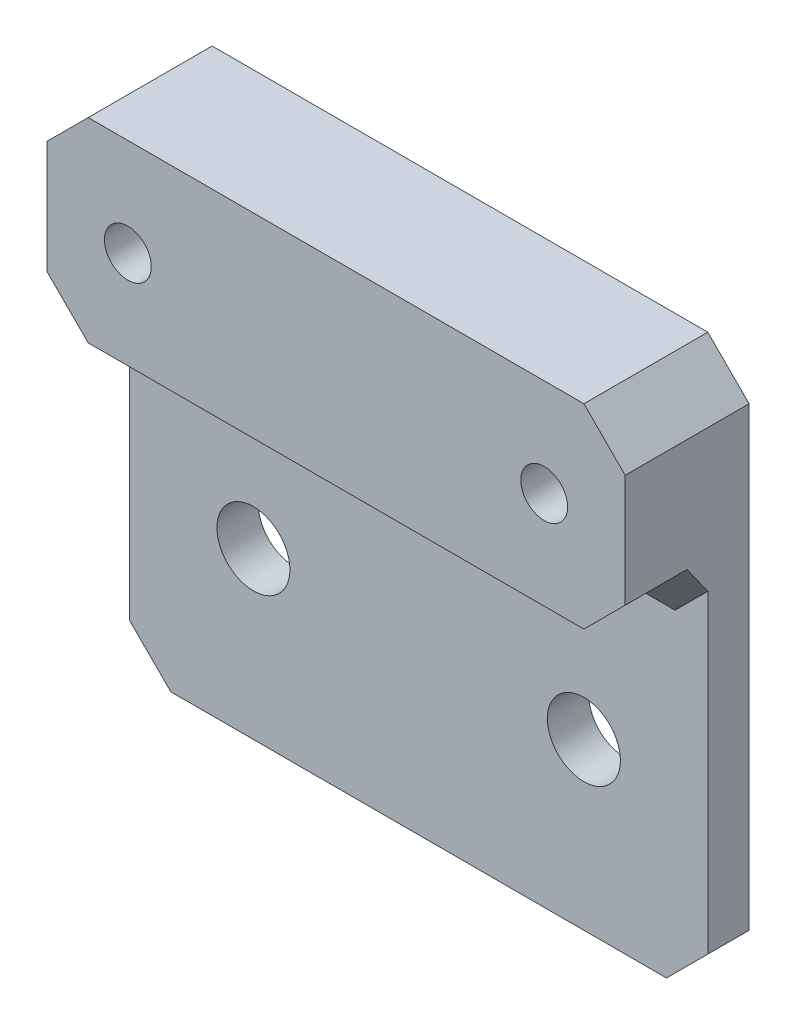
SolidWorks part; units mm, degrees
ref_plane "Front" through (0, 0, 0) normal (0, 0, 1) x (1, 0, 0)
ref_plane "Top" through (0, 0, 0) normal (0, 1, 0) x (1, 0, 0)
ref_plane "Right" through (0, 0, 0) normal (1, 0, 0) x (0, 0, -1)
sketch "Sketch1" plane through (0, 0, 0) normal (0, 0, 1) x (1, 0, 0)
  line L0 (-22.225, 0) -> (-12.7, 0) construction
  line L1 (-22.225, 12.7) -> (22.225, 12.7) construction
  line L2 (-22.225, 12.7) -> (-22.225, -12.7)
  line L3 (-22.225, -12.7) -> (22.225, -12.7)
  line L4 (22.225, 12.7) -> (22.225, -12.7)
  line L5 (-22.225, 12.7) -> (22.225, -12.7) construction
  line L6 (-22.225, -12.7) -> (22.225, 12.7) construction
  line L7 (-12.7, 0) -> (12.7, 0) construction
  line L8 (12.7, 0) -> (22.225, 0) construction
  line L9 (-22.225, 13.7) -> (-22.225, 28.7)
  line L10 (-22.225, 28.7) -> (22.225, 28.7)
  line L11 (22.225, 28.7) -> (22.225, 13.7)
  line L12 (-22.225, 13.7) -> (22.225, 13.7) construction
  line L13 (22.225, 13.7) -> (22.225, 12.7)
  line L14 (-22.225, 13.7) -> (-22.225, 12.7)
  point P0 (0, 0)
  dimension "D1" = 25.4
  dimension "D2" = 44.45
  dimension "D3" = 25.4
  dimension "D4" = 15
  dimension "D5" = 1
extrude "Boss-Extrude1" add sketch "Sketch1" along normal blind 3.175
sketch "Sketch2" plane through (0, 0, 3.175) normal (0, 0, 1) x (1, 0, 0)
  line L1 (-22.225, 28.7) -> (22.225, 28.7)
  line L2 (-22.225, 28.7) -> (-22.225, 13.7)
  line L3 (-22.225, 13.7) -> (22.225, 13.7)
  line L4 (22.225, 28.7) -> (22.225, 13.7)
  point P5 (0, 0)
  point P7 (0, 0)
  point P8 (20.5488, 16.1821)
extrude "Boss-Extrude2" add sketch "Sketch2" along normal blind 6.35
sketch "Sketch3" plane through (0, 0, 9.525) normal (0, 0, 1) x (1, 0, 0)
  line L0 (-22.225, 21.2) -> (-16, 21.2) construction
  line L1 (-22.225, 28.7) -> (-22.225, 13.7) construction
  line L2 (-16, 21.2) -> (16, 21.2) construction
  line L3 (16, 21.2) -> (22.225, 21.2) construction
  line L4 (22.225, 13.7) -> (22.225, 28.7) construction
  dimension "D1" = 32
hole_wizard "CBORE for M3 Hex Head Machine Screw1" positions "Sketch5" profile "Sketch6" counterbore size "M3" standard "ANSI Metric" end condition through all
sketch "Sketch5" plane through (0, 0, 0) normal (0, 0, -1) x (-1, 0, 0)
  point P0 (-16, 21.2)
  point P2 (16, 21.2)
  point P6 (0, 0)
sketch "Sketch6" plane through (16, 21.2, 0) normal (1, 0, 0) x (0, 1, 0)
  line L0 (0, 0) -> (0, 9.525)
  line L1 (0, 9.525) -> (1.8, 9.525)
  line L3 (1.8, 9.525) -> (1.8, 2.3)
  line L4 (1.8, 2.3) -> (4.2, 2.3)
  line L5 (4.2, 2.3) -> (4.2, 0)
  line L7 (4.2, 0) -> (0, 0)
  line L11 (0, -6.35) -> (0, 107.95) construction
  dimension "Thru Hole Dia." = 3.6
  dimension "Thru Hole Depth" = 9.525
  dimension "C'Bore Dia." = 8.4
  dimension "C'Bore Depth" = 2.3
chamfer "Chamfer2" distance 3.175 angle 45 6 edges at (22.225, 13.7, 6.35) (-22.225, 13.7, 6.35) (-22.225, 28.7, 4.7625) (22.225, 28.7, 4.7625) (22.225, -12.7, 1.5875) (-22.225, -12.7, 1.5875)
chamfer "Chamfer1" distance 1.5875 angle 45 3 edges at (0, 13.7, 3.175) (20.6375, 15.2875, 3.175) (-20.6375, 15.2875, 3.175)
hole_wizard "#10 Clearance Hole1" positions "Sketch7" profile "Sketch8" hole size "#10" standard "ANSI Inch" end condition through all
sketch "Sketch7" plane through (0, 0, 3.175) normal (0, 0, 1) x (1, 0, 0)
  point P0 (-12.7, 0)
  point P2 (12.7, 0)
sketch "Sketch8" plane through (-12.7, 0, 3.175) normal (1, 0, 0) x (0, -1, 0)
  line L0 (0, 0) -> (0, 3.175)
  line L1 (0, 3.175) -> (2.8067, 3.175)
  line L2 (2.8067, 3.175) -> (2.8067, 0)
  line L5 (2.8067, 0) -> (0, 0)
  line L11 (0, -6.35) -> (0, 107.95) construction
  dimension "Thru Hole Dia." = 5.6134
  dimension "Thru Hole Depth" = 3.175
